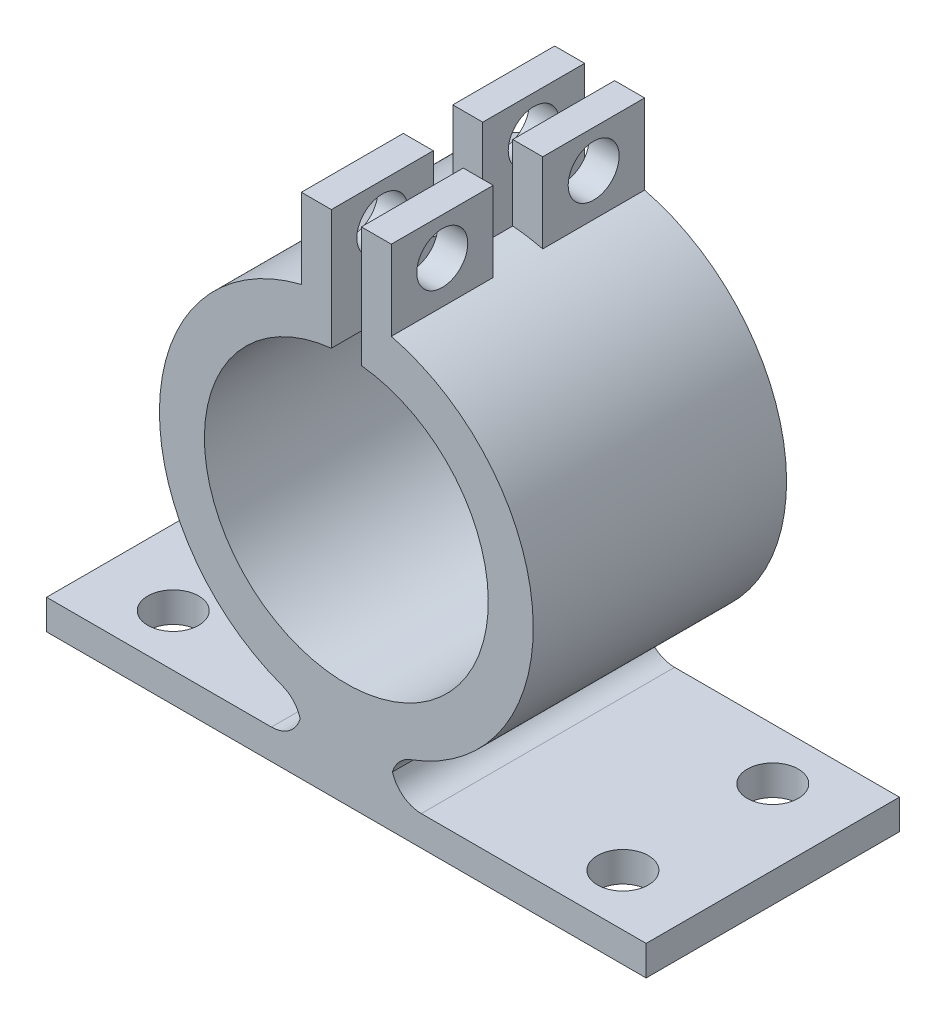
SolidWorks part; units mm, degrees
ref_plane "Front Plane" through (0, 0, 0) normal (0, 0, 1) x (1, 0, 0)
ref_plane "Top Plane" through (0, 0, 0) normal (0, 1, 0) x (1, 0, 0)
ref_plane "Right Plane" through (0, 0, 0) normal (1, 0, 0) x (0, 0, -1)
sketch "Sketch1" plane through (0, 0, 0) normal (0, 0, 1) x (1, 0, 0)
  line L2 (-1, 9.4171) -> (-1, 12.4298)
  line L4 (1, 9.4171) -> (1, 12.4298)
  line L5 (0, 9.47) -> (0.7216, 12.4491) construction
  line L6 (-0.7216, 12.4491) -> (0, 9.47) construction
  line L9 (-3, -12.1038) -> (-3, -16.47)
  line L10 (-3, -16.47) -> (3, -16.47)
  line L11 (3, -12.1038) -> (3, -16.47)
  line L12 (0, -12.47) -> (3, -16.47) construction
  line L13 (-3, -16.47) -> (0, -12.47) construction
  circle A0 centre (0, 0) radius 9.47
  arc A1 (3, -12.1038) -> (-3, -12.1038) centre (0, 0) ccw
  circle A2 centre (0, 0) radius 12.47 construction
  point P5 (0, 9.47)
  point P6 (-1, 10.9234)
  point P16 (0, -12.47)
  dimension "D1" = 18.94
  dimension "D3" = 2
  dimension "D4" = 4
  dimension "D5" = 3
  dimension "D6" = 3
  dimension "D2" = 3
extrude "Boss-Extrude1" add sketch "Sketch1" along normal blind 16.9 contours L2 A1 L4 A0 region at (-6.5882, -7.3248, 0)
sketch "Sketch2" plane through (-1, 0, 0) normal (1, 0, 0) x (0, 0, -1)
  line L0 (-8.45, 12.4298) -> (-8.45, 9.4171) construction
  line L1 (-16.9, 12.4298) -> (-10.1, 12.4298)
  line L2 (-16.9, 12.4298) -> (-16.9, 17.4298)
  line L3 (-16.9, 17.4298) -> (-10.1, 17.4298)
  line L4 (-10.1, 12.4298) -> (-10.1, 17.4298)
  line L5 (-16.9, 12.4298) -> (0, 12.4298) construction
  line L6 (-16.9, 9.4171) -> (0, 9.4171) construction
  line L7 (-6.8, 12.4298) -> (-6.8, 17.4298)
  line L8 (0, 17.4298) -> (-6.8, 17.4298)
  line L9 (0, 12.4298) -> (0, 17.4298)
  line L10 (0, 12.4298) -> (-6.8, 12.4298)
  circle A0 centre (-13.5, 14.9298) radius 1.7
  circle A1 centre (-3.4, 14.9298) radius 1.7
  dimension "D2" = 3.4
  dimension "D1" = 6.8
  dimension "D3" = 5
extrude "Boss-Extrude2" add sketch "Sketch2" against normal blind 2 separate body
sketch "Sketch5" plane through (0, 12.4298, 0) normal (0, -1, 0) x (1, 0, 0)
  line L1 (-3, 6.8) -> (-1, 6.8)
  line L2 (-3, 6.8) -> (-3, 0)
  line L3 (-3, 0) -> (-1, 0)
  line L4 (-1, 6.8) -> (-1, 0)
  line L5 (-3, 10.1) -> (-1, 10.1)
  line L6 (-3, 10.1) -> (-3, 16.9)
  line L7 (-3, 16.9) -> (-1, 16.9)
  line L8 (-1, 10.1) -> (-1, 16.9)
extrude "Boss-Extrude3" add sketch "Sketch5" along normal up to body
sketch "Sketch7" plane through (1, 0, 0) normal (-1, 0, 0) x (0, 0, 1)
  line L0 (0, 12.4298) -> (6.8, 12.4298)
  line L1 (0, 12.4298) -> (0, 17.4298)
  line L2 (0, 17.4298) -> (6.8, 17.4298)
  line L3 (6.8, 12.4298) -> (6.8, 17.4298)
  line L4 (10.1, 12.4298) -> (10.1, 17.4298)
  line L5 (16.9, 17.4298) -> (10.1, 17.4298)
  line L6 (16.9, 12.4298) -> (16.9, 17.4298)
  line L7 (16.9, 12.4298) -> (10.1, 12.4298)
  circle A0 centre (3.4, 14.9298) radius 1.7
  circle A1 centre (13.5, 14.9298) radius 1.7
  dimension "D1" = 3.4
  dimension "D2" = 5
extrude "Boss-Extrude4" add sketch "Sketch7" against normal blind 2 separate body
sketch "Sketch8" plane through (0, 12.4298, 0) normal (0, -1, 0) x (1, 0, 0)
  line L1 (3, 6.8) -> (1, 6.8)
  line L2 (3, 6.8) -> (3, 0)
  line L3 (3, 0) -> (1, 0)
  line L4 (1, 6.8) -> (1, 0)
  line L5 (3, 10.1) -> (1, 10.1)
  line L6 (3, 10.1) -> (3, 16.9)
  line L7 (3, 16.9) -> (1, 16.9)
  line L8 (1, 10.1) -> (1, 16.9)
extrude "Boss-Extrude5" add sketch "Sketch8" along normal up to body
sketch "Sketch9" plane through (-3, 0, 0) normal (-1, 0, 0) x (0, 0, 1)
  line L0 (16.9, -12.1038) -> (16.9, -16.47) construction
  line L1 (0, -16.47) -> (16.9, -16.47)
  line L2 (0, -16.47) -> (0, -14.47)
  line L3 (0, -14.47) -> (16.9, -14.47)
  line L4 (16.9, -16.47) -> (16.9, -14.47)
  dimension "D1" = 2
extrude "Boss-Extrude7" add sketch "Sketch9" along normal blind 17 and the other way blind 23
sketch "Sketch10" plane through (0, -16.47, 0) normal (0, -1, 0) x (1, 0, 0)
  line L0 (0, 16.9) -> (0, 0) construction
  line L1 (-20, 16.9) -> (20, 16.9) construction
  line L2 (-20, 0) -> (20, 0) construction
  line L3 (-20, 8.45) -> (20, 8.45) construction
  line L4 (-20, 0) -> (-20, 16.9) construction
  line L5 (20, 0) -> (20, 16.9) construction
  circle A0 centre (-15, 3.45) radius 1.7
  circle A1 centre (-15, 13.45) radius 1.7
  circle A2 centre (15, 3.45) radius 1.7
  circle A3 centre (15, 13.45) radius 1.7
  dimension "D1" = 3.4
  dimension "D2" = 30
  dimension "D3" = 10
  dimension "D4" = 15
  dimension "D5" = 16.9
  dimension "D6" = 5
extrude "Cut-Extrude1" cut sketch "Sketch10" against normal up to next
fillet "Fillet1" radius 2 4 edges at (-3, -12.1038, 8.45) (-3, -14.47, 8.45) (3, -12.1038, 8.45) (3, -14.47, 8.45)
